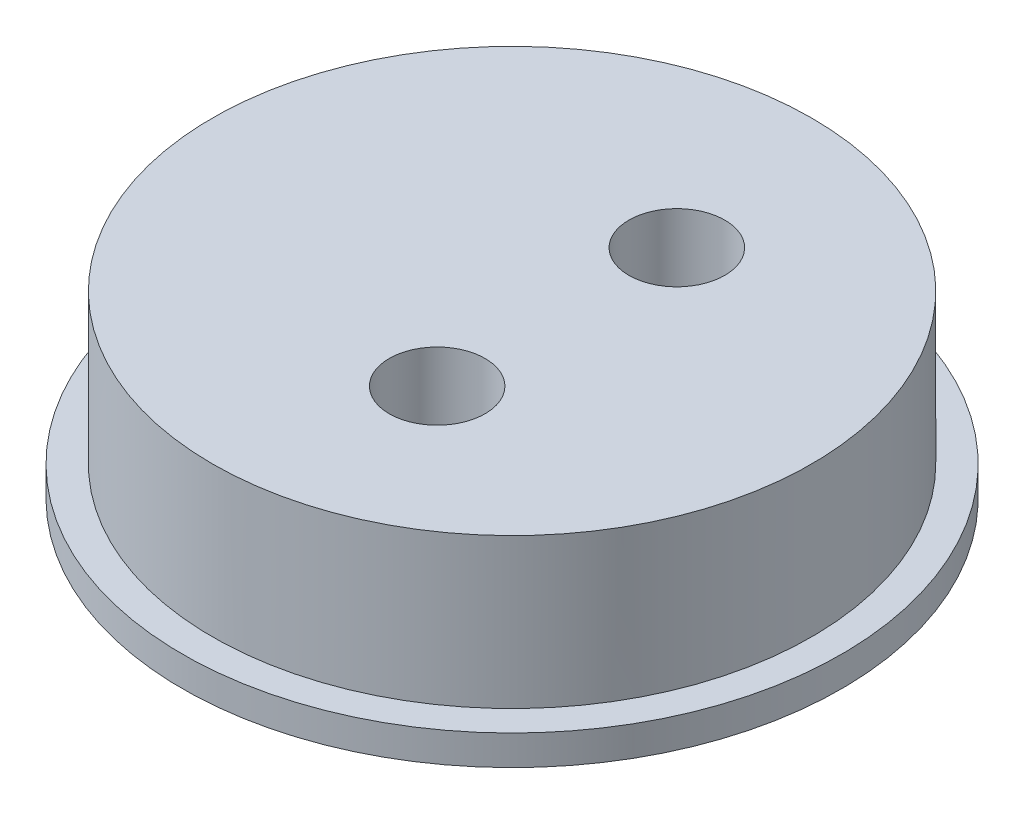
SolidWorks part; units mm, degrees
ref_plane "Front Plane" through (0, 0, 0) normal (0, 0, 1) x (1, 0, 0)
ref_plane "Top Plane" through (0, 0, 0) normal (0, 1, 0) x (1, 0, 0)
ref_plane "Right Plane" through (0, 0, 0) normal (1, 0, 0) x (0, 0, -1)
sketch "Sketch1" plane through (0, 0, 0) normal (0, 1, 0) x (1, 0, 0)
  line L0 (0, 0) -> (-1.5, 0) construction
  circle A1 centre (-1.5, 0) radius 10
  point P12 (0, 0)
  dimension "D3" = 20
  dimension "D2" = 1.5
extrude "Boss-Extrude1" add sketch "Sketch1" along normal blind 6
sketch "Sketch2" plane through (0, 0, 0) normal (0, -1, 0) x (1, 0, 0)
  line L0 (-12.8187, 0) -> (7.6603, 0) construction
  circle A0 centre (-1.5, 0) radius 11
  dimension "D2" = 22
  dimension "D1" = 1.5
extrude "Boss-Extrude2" add sketch "Sketch2" against normal blind 1
sketch "Sketch4" plane through (0, 6, 0) normal (0, 1, 0) x (1, 0, 0)
  line L0 (0, 8.8969) -> (0, -8.7328) construction
  circle A0 centre (0, 0) radius 4 construction
  circle A1 centre (0, 4) radius 1.6
  circle A2 centre (0, -4) radius 1.6
  dimension "D1" = 8
  dimension "D2" = 3.2
extrude "Cut-Extrude1" cut sketch "Sketch4" against normal through all
